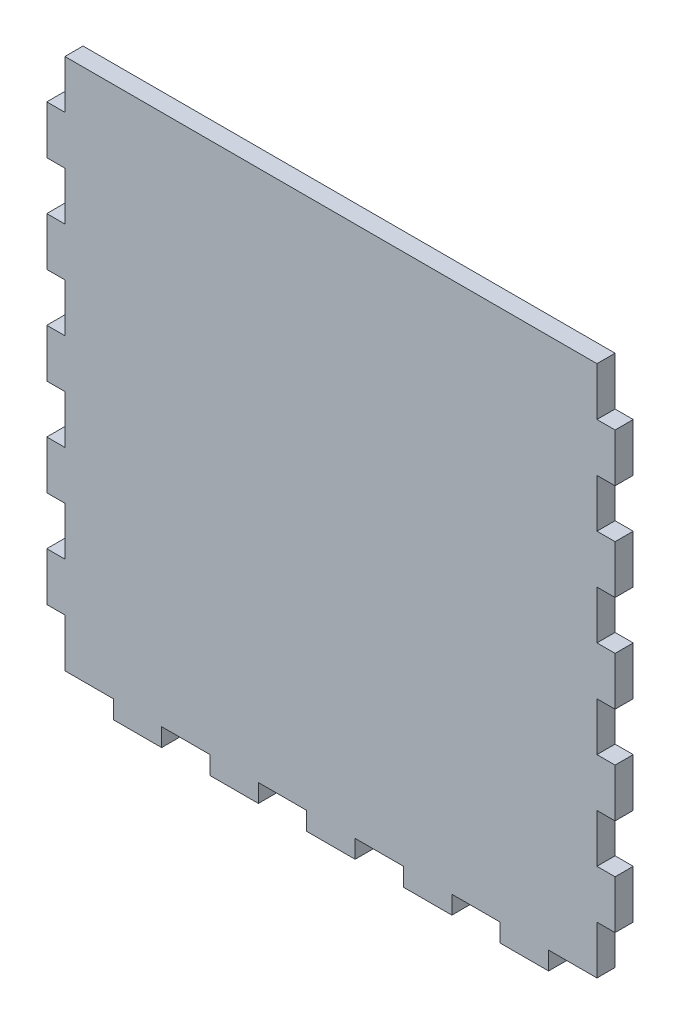
SolidWorks part; units mm, degrees
ref_plane "Front Plane" through (0, 0, 0) normal (0, 0, 1) x (1, 0, 0)
ref_plane "Top Plane" through (0, 0, 0) normal (0, 1, 0) x (1, 0, 0)
ref_plane "Right Plane" through (0, 0, 0) normal (1, 0, 0) x (0, 0, -1)
sketch "Sketch2" plane through (0, 0, 0) normal (0, 0, 1) x (1, 0, 0)
  line L1 (-139.7, -139.7) -> (139.7, -139.7)
  line L2 (-139.7, -139.7) -> (-139.7, 139.7)
  line L3 (-139.7, 139.7) -> (139.7, 139.7)
  line L4 (139.7, -139.7) -> (139.7, 139.7)
  line L5 (-139.7, -139.7) -> (139.7, 139.7) construction
  line L6 (-139.7, 139.7) -> (139.7, -139.7) construction
  point P0 (0, 0)
  dimension "D1" = 279.4
  dimension "D2" = 279.4
extrude "Boss-Extrude1" add sketch "Sketch2" along normal blind 9.525
sketch "Sketch3" plane through (0, 139.7, 0) normal (0, 1, 0) x (1, 0, 0)
  line L0 (-158.9087, 0) -> (158.9087, 0) construction
  line L1 (-114.3, -9.525) -> (-88.9, -9.525)
  line L2 (-114.3, -9.525) -> (-114.3, 0)
  line L3 (-114.3, 0) -> (-88.9, 0)
  line L4 (-88.9, -9.525) -> (-88.9, 0)
  line L6 (-139.7, -9.525) -> (-139.7, 0) construction
  dimension "D1" = 25.4
  dimension "D2" = 25.4
sketch "Sketch4" plane through (139.7, 0, 0) normal (1, 0, 0) x (0, 0, -1)
  line L0 (0, 158.9087) -> (0, -158.9087) construction
  line L1 (0, -114.3) -> (-9.525, -114.3)
  line L2 (0, -114.3) -> (0, -88.9)
  line L3 (0, -88.9) -> (-9.525, -88.9)
  line L4 (-9.525, -114.3) -> (-9.525, -88.9)
  line L5 (-9.525, -139.7) -> (-9.525, 139.7) construction
  line L7 (-9.525, -139.7) -> (0, -139.7) construction
  dimension "D1" = 25.4
  dimension "D2" = 25.4
extrude "Boss-Extrude3" add sketch "Sketch4" along normal blind 9.525
pattern_linear "LPattern2" count 5 spacing 50.8 along (0, 1, 0) of "Boss-Extrude3"
mirror "Mirror2" about plane through (0, 0, 0) normal (1, 0, 0) of "LPattern2"
sketch "Sketch5" plane through (0, -139.7, 0) normal (0, -1, 0) x (1, 0, 0)
  line L1 (-114.3, 9.525) -> (-88.9, 9.525)
  line L2 (-114.3, 9.525) -> (-114.3, 0)
  line L3 (-114.3, 0) -> (-88.9, 0)
  line L4 (-88.9, 9.525) -> (-88.9, 0)
extrude "Boss-Extrude4" add sketch "Sketch5" along normal blind 9.525
pattern_linear "LPattern3" count 5 spacing 50.8 along (1, 0, 0) of "Boss-Extrude4"
